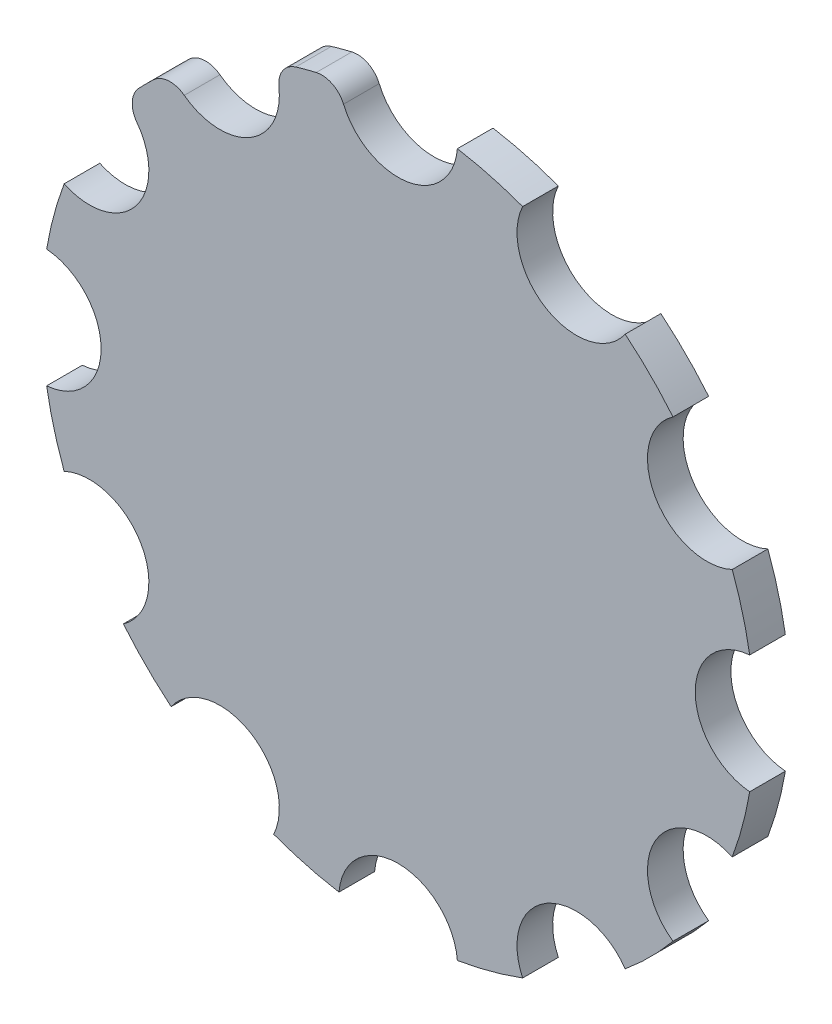
SolidWorks part; units mm, degrees
ref_plane "Front Plane" through (0, 0, 0) normal (0, 0, 1) x (1, 0, 0)
ref_plane "Top Plane" through (0, 0, 0) normal (0, 1, 0) x (1, 0, 0)
ref_plane "Right Plane" through (0, 0, 0) normal (1, 0, 0) x (0, 0, -1)
sketch "Sketch1" plane through (0, 0, 0) normal (0, 0, 1) x (1, 0, 0)
  line L0 (0, 25) -> (0, 30) construction
  circle A0 centre (0, 0) radius 30
  circle A1 centre (0, 0) radius 25 construction
  circle A2 centre (0, 30) radius 5
  circle A3 centre (15, 25.9808) radius 5
  circle A4 centre (25.9808, 15) radius 5
  circle A5 centre (30, 0) radius 5
  circle A6 centre (25.9808, -15) radius 5
  circle A7 centre (15, -25.9808) radius 5
  circle A8 centre (0, -30) radius 5
  circle A9 centre (-15, -25.9808) radius 5
  circle A10 centre (-25.9808, -15) radius 5
  circle A11 centre (-30, 0) radius 5
  circle A12 centre (-25.9808, 15) radius 5
  circle A13 centre (-15, 25.9808) radius 5
  point P31 (0, 0)
  dimension "D1" = 60
  dimension "D2" = 50
  dimension "D3" = 12
extrude "Boss-Extrude1" add sketch "Sketch1" along normal blind 3 contours A13 A0 A12 A11 A10 A9 A8 A7 A6 A5 A4 A3 A2 region at (0, 0, 0)
fillet "Fillet1" radius 2 4 edges at (-23.1286, 19.1067, 1.5) (-19.1067, 23.1286, 1.5) (-4.9826, 29.5833, 1.5) (-10.4766, 28.1112, 1.5)
